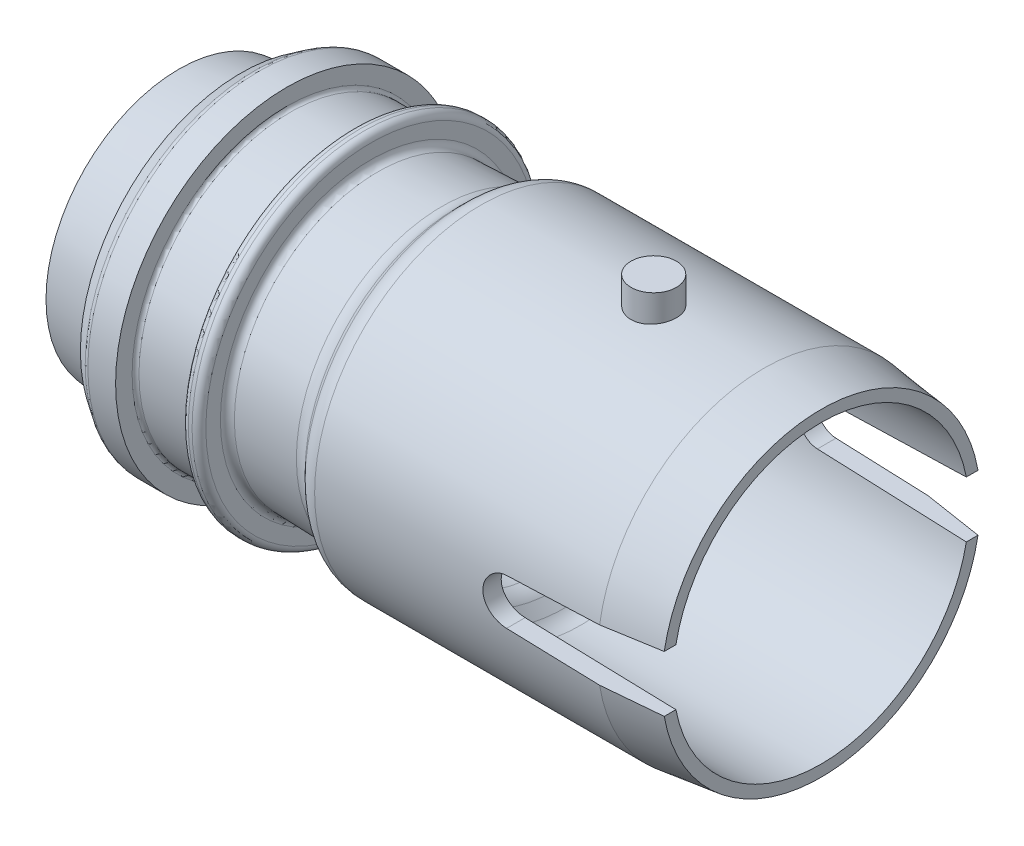
SolidWorks part; units mm, degrees
ref_plane "Front Plane" through (0, 0, 0) normal (0, 0, 1) x (1, 0, 0)
ref_plane "Top Plane" through (0, 0, 0) normal (0, 1, 0) x (1, 0, 0)
ref_plane "Right Plane" through (0, 0, 0) normal (1, 0, 0) x (0, 0, -1)
sketch "Sketch1" plane through (0, 0, 0) normal (0, 0, 1) x (1, 0, 0)
  line L0 (-11.7761, 0) -> (32.5958, 0) construction
  line L1 (-40.64, 13.7795) -> (0, 13.7795)
  line L2 (0, 13.7795) -> (0, 16.383)
  line L3 (0, 16.383) -> (30.48, 16.383)
  line L8 (-40.64, 14.732) -> (-40.64, 13.7795)
  line L9 (-7.62, 18.415) -> (24.13, 18.415)
  line L10 (24.13, 18.415) -> (30.48, 17.653)
  line L11 (30.48, 17.653) -> (30.48, 16.383)
  line L12 (-40.64, 14.732) -> (-33.782, 15.621)
  line L13 (-33.782, 15.621) -> (-33.782, 17.78)
  line L14 (-33.782, 17.78) -> (-32.004, 18.9611)
  line L15 (-32.004, 18.9611) -> (-28.702, 18.9611)
  line L16 (-28.702, 18.9611) -> (-28.702, 16.7513)
  line L17 (-28.702, 16.7513) -> (-21.336, 16.7513)
  line L18 (-21.336, 16.7513) -> (-21.336, 19.0373)
  line L19 (-21.336, 19.0373) -> (-19.3929, 19.0373)
  line L20 (-19.3929, 19.0373) -> (-19.3929, 15.875)
  line L21 (-19.3929, 15.875) -> (-7.62, 16.256)
  line L22 (-7.62, 18.415) -> (-7.62, 16.256)
  dimension "D1" = 36.83
  dimension "D2" = 32.766
  dimension "D3" = 35.306
  dimension "D4" = 38.1
  dimension "D5" = 27.559
  dimension "D6" = 29.464
  dimension "D7" = 6.858
  dimension "D8" = 6.35
  dimension "D9" = 30.48
  dimension "D10" = 7.366
  dimension "D11" = 1.9431
  dimension "D12" = 31.242
  dimension "D13" = 37.9222
  dimension "D14" = 5.08
  dimension "D15" = 33.5026
  dimension "D16" = 31.75
  dimension "D17" = 32.512
  dimension "D18" = 35.56
  dimension "D19" = 3.302
  dimension "D20" = 33.02
  dimension "D21" = 38.0746
revolve "Revolve1" add sketch "Sketch1" angle 360 about L0
sketch "Sketch2" plane through (0, 0, 0) normal (0, 0, 1) x (1, 0, 0)
  line L0 (13.8824, 2.5385) -> (30.48, 3.1115)
  line L1 (30.48, 3.1115) -> (30.48, -3.1115)
  line L2 (30.48, -3.1115) -> (13.8824, -2.5385)
  line L4 (55, 0) -> (-55, 0) construction
  line L5 (30.48, -17.653) -> (30.48, 17.653) construction
  arc A0 (13.8824, 2.5385) -> (13.8824, -2.5385) centre (13.97, 0) ccw
  dimension "D1" = 2.54
  dimension "D3" = 16.51
  dimension "D2" = 6.223
extrude "Cut-Extrude3" cut sketch "Sketch2" against normal through all both and the other way through all
ref_plane "Plane1" through (0, 21.336, 0) normal (0, 1, 0) x (1, 0, 0)
sketch "Sketch3" plane through (0, 21.336, 0) normal (0, 1, 0) x (1, 0, 0)
  line L0 (30.48, -17.3766) -> (30.48, 17.3766) construction
  circle A0 centre (11.938, 0) radius 2.5146
  dimension "D1" = 5.0292
  dimension "D2" = 18.542
extrude "Boss-Extrude1" add sketch "Sketch3" against normal up to surface (3.0935 mm away) up to face at (-7.62, 0, 18.415)
mirror "Mirror1" about plane through (0, 0, 0) normal (0, 1, 0) of "Boss-Extrude1"
fillet "Fillet1" radius 0.762 5 edges at (-32.004, 0, 18.9611) (-19.3929, 0, 15.875) (-21.336, 0, 16.7513) (-21.336, 0, 19.0373) (-19.3929, 0, 19.0373)
chamfer "Chamfer1" distance 2.794 angle 45 2 edges at (0, 0, 16.383) (-7.62, 0, 16.256) first distance on face at (0, 0, 16.383) first distance on face at (-7.62, 0, 16.256)
fillet "Fillet2" radius 0.381 2 edges at (-28.702, 0, 16.7513) (-33.782, 0, 15.621)
fillet "Fillet3" radius 2.54 4 edges at (2.794, 0, 16.383) (-8.255, 0, -18.415) (-10.5074, 0, -16.1626) (0.1905, 0, -13.7795)
